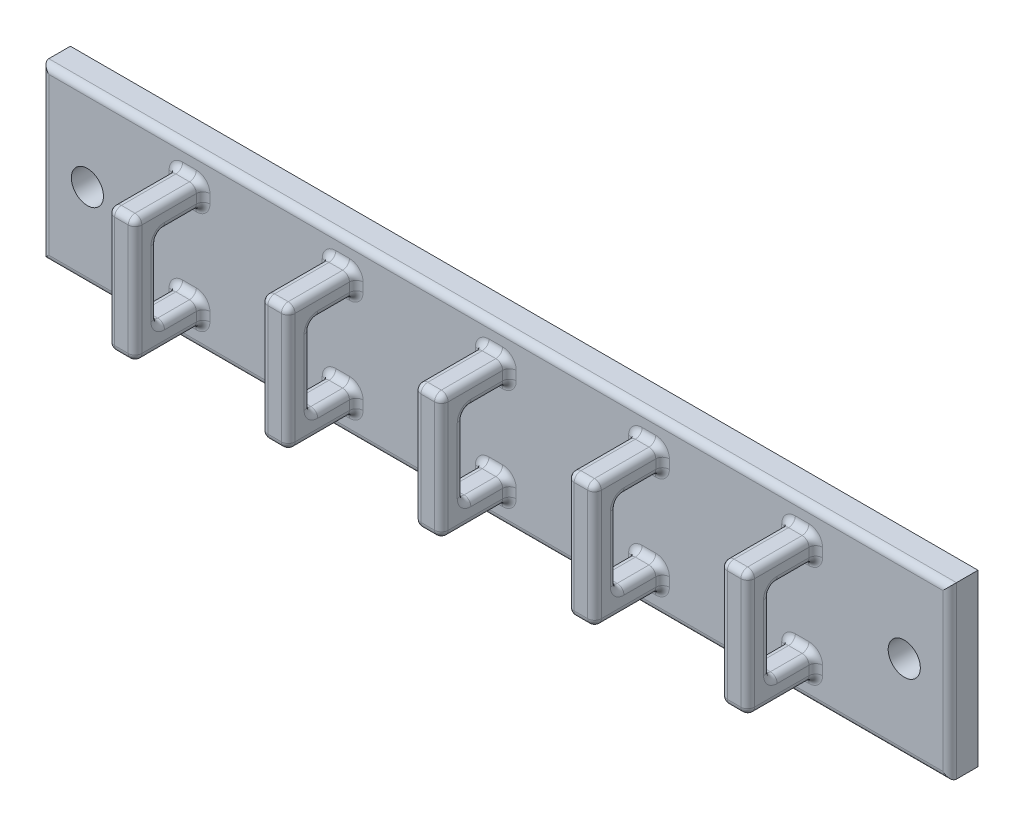
SolidWorks part; units mm, degrees
ref_plane "Front Plane" through (0, 0, 0) normal (0, 0, 1) x (1, 0, 0)
ref_plane "Top Plane" through (0, 0, 0) normal (0, 1, 0) x (1, 0, 0)
ref_plane "Right Plane" through (0, 0, 0) normal (1, 0, 0) x (0, 0, -1)
sketch "Sketch2" plane through (0, 0, 0) normal (0, 0, 1) x (1, 0, 0)
  line L1 (0, 0) -> (101.6, 0)
  line L2 (0, 0) -> (0, 19.05)
  line L3 (0, 19.05) -> (101.6, 19.05)
  line L4 (101.6, 0) -> (101.6, 19.05)
  dimension "D1" = 101.6
  dimension "D2" = 19.05
extrude "Boss-Extrude1" add sketch "Sketch2" along normal blind 3.175
hole_wizard "M3 Clearance Hole1" positions "Sketch3" profile "Sketch4" hole size "M3" standard "ANSI Metric" end condition through all
sketch "Sketch3" plane through (0, 0, 3.175) normal (0, 0, 1) x (1, 0, 0)
  line L0 (0, 19.05) -> (0, 0) construction
  line L1 (101.6, 0) -> (101.6, 19.05) construction
  line L2 (0, 0) -> (101.6, 0) construction
  point P0 (5.08, 9.525)
  point P2 (96.52, 9.525)
  dimension "D1" = 5.08
  dimension "D2" = 5.08
  dimension "D3" = 9.525
sketch "Sketch4" plane through (5.08, 9.525, 3.175) normal (1, 0, 0) x (0, -1, 0)
  line L0 (0, 0) -> (0, 3.175)
  line L1 (0, 3.175) -> (1.8, 3.175)
  line L2 (1.8, 3.175) -> (1.8, 0)
  line L5 (1.8, 0) -> (0, 0)
  line L11 (0, -6.35) -> (0, 107.95) construction
  dimension "Thru Hole Dia." = 3.6
  dimension "Thru Hole Depth" = 3.175
ref_plane "Plane2" through (16.51, 0, 0) normal (-1, 0, 0) x (0, 0, 1)
sketch "Sketch6" plane through (16.51, 0, 0) normal (-1, 0, 0) x (0, 0, 1)
  line L0 (3.175, 16.51) -> (10.795, 16.51)
  line L1 (10.795, 16.51) -> (10.795, 2.54)
  line L2 (10.795, 2.54) -> (3.175, 2.54)
  line L3 (3.175, 19.05) -> (3.175, 0) construction
  line L4 (3.175, 2.54) -> (3.175, 5.08)
  line L5 (3.175, 5.08) -> (8.255, 5.08)
  line L6 (8.255, 5.08) -> (8.255, 13.97)
  line L7 (8.255, 13.97) -> (3.175, 13.97)
  line L8 (3.175, 13.97) -> (3.175, 16.51)
  line L9 (3.175, 19.05) -> (0, 19.05) construction
  point P2 (3.175, 9.525)
  point P11 (8.255, 9.525)
  dimension "D1" = 2.54
  dimension "D2" = 2.54
  dimension "D3" = 2.54
  dimension "D4" = 5.08
extrude "Boss-Extrude3" add sketch "Sketch6" along normal blind 1.524 and the other way blind 1.524
fillet "Fillet2" radius 0.762 24 edges at (16.51, 16.51, 3.175) (16.51, 2.54, 3.175) (16.51, 5.08, 3.175) (16.51, 13.97, 3.175) (16.51, 13.97, 8.255) (16.51, 5.08, 8.255) (18.034, 13.97, 5.715) (18.034, 9.525, 8.255) (18.034, 5.08, 5.715) (18.034, 3.81, 3.175) (18.034, 2.54, 6.985) (18.034, 9.525, 10.795) (18.034, 16.51, 6.985) (18.034, 15.24, 3.175) (14.986, 16.51, 6.985) (14.986, 9.525, 10.795) (14.986, 2.54, 6.985) (14.986, 3.81, 3.175) (14.986, 5.08, 5.715) (14.986, 9.525, 8.255) (14.986, 13.97, 5.715) (14.986, 15.24, 3.175) (16.51, 2.54, 10.795) (16.51, 16.51, 10.795)
pattern_linear "LPattern2" count 5 spacing 17.145 along (1, 0, 0) of "Boss-Extrude3", "Fillet2"
fillet "Fillet3" radius 0.762 4 edges at (101.6, 9.525, 3.175) (50.8, 0, 3.175) (0, 9.525, 3.175) (50.8, 19.05, 3.175)
